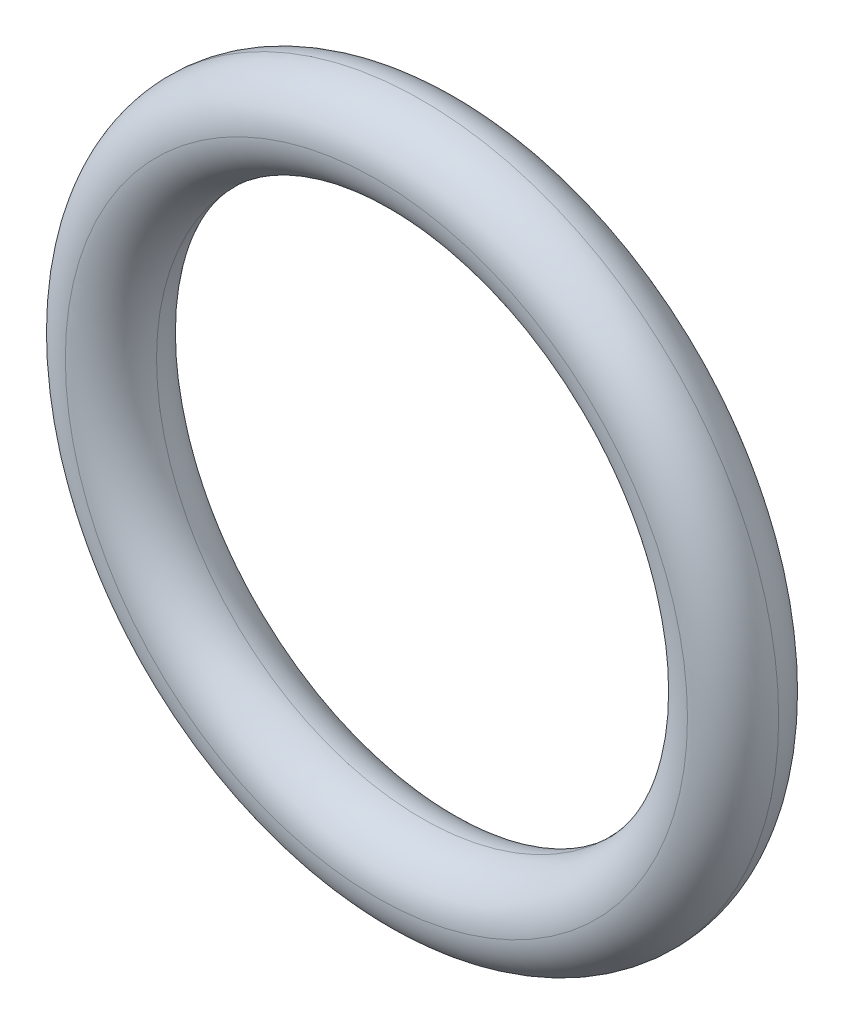
SolidWorks part; units mm, degrees
material "Rubber"
ref_plane "Front Plane" through (0, 0, 0) normal (0, 0, 1) x (1, 0, 0)
ref_plane "Top Plane" through (0, 0, 0) normal (0, 1, 0) x (1, 0, 0)
ref_plane "Right Plane" through (0, 0, 0) normal (1, 0, 0) x (0, 0, -1)
other "Configuration Table"
sketch "Sketch2" plane through (0, 0, 0) normal (0, 0, 1) x (1, 0, 0)
  circle A0 centre (0, 0) radius 9.5377
  circle A1 centre (0, 0) radius 7.0993
  dimension "D1" = 14.1986
  dimension "D2" = 19.0754
extrude "Boss-Extrude1" add sketch "Sketch2" against normal blind 2.4384
fillet "Fillet3" radius 1.2192 4 edges at (7.0993, 0, -2.4384) (7.0993, 0, 0) (9.5377, 0, -2.4384) (9.5377, 0, 0)
